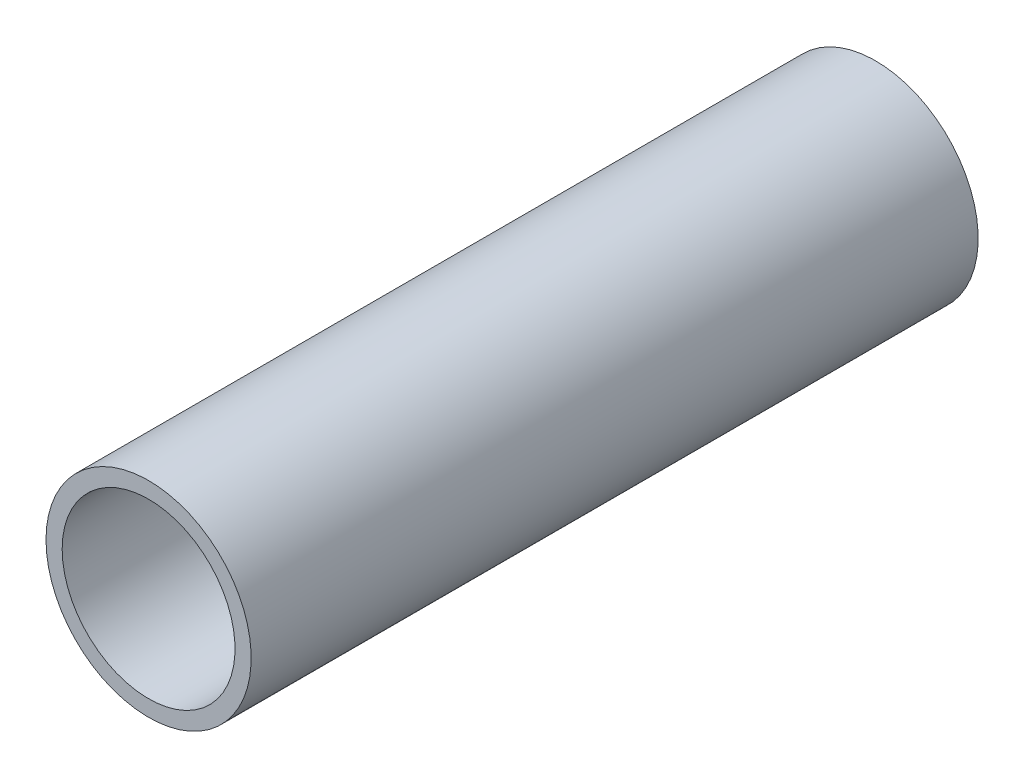
SolidWorks part; units mm, degrees
material "Hexcel AS4C (3000 Filaments)"
ref_plane "Front Plane" through (0, 0, 0) normal (0, 0, 1) x (1, 0, 0)
ref_plane "Top Plane" through (0, 0, 0) normal (0, 1, 0) x (1, 0, 0)
ref_plane "Right Plane" through (0, 0, 0) normal (1, 0, 0) x (0, 0, -1)
sketch "Sketch1" plane through (0, 0, 0) normal (0, 0, 1) x (1, 0, 0)
  circle A0 centre (0, 0) radius 12.7
  circle A1 centre (0, 0) radius 10.7
  dimension "D1" = 25.4
  dimension "D2" = 2
extrude "Boss-Extrude1" add sketch "Sketch1" along normal blind 90
